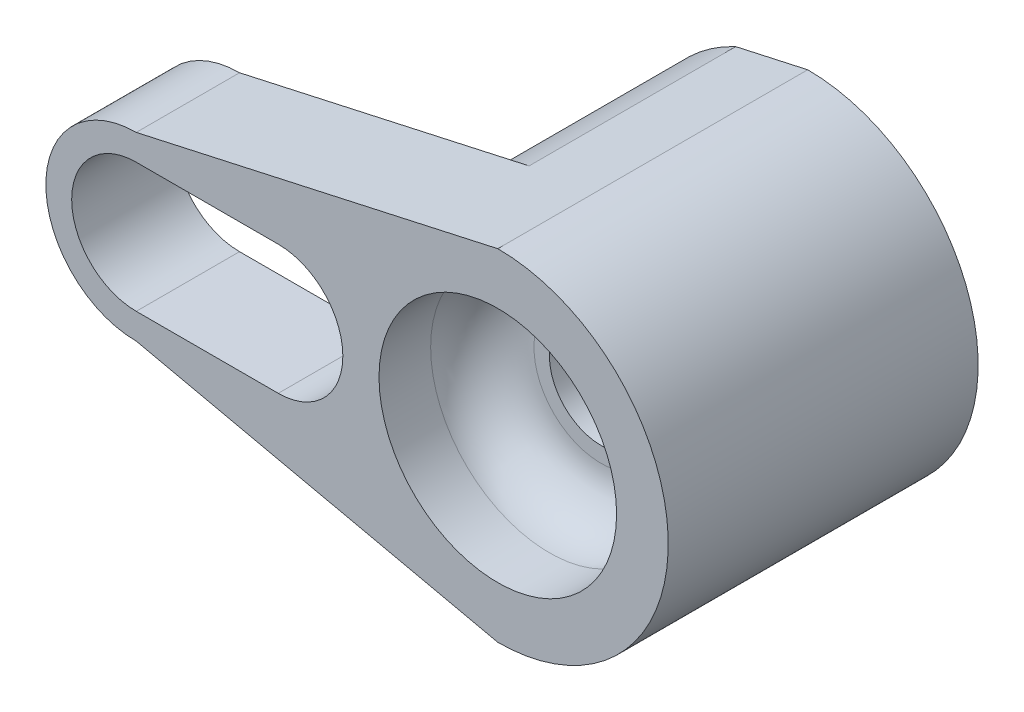
SolidWorks part; units mm, degrees
ref_plane "Ebene vorne" through (0, 0, 0) normal (0, 0, 1) x (1, 0, 0)
ref_plane "Ebene oben" through (0, 0, 0) normal (0, 1, 0) x (1, 0, 0)
ref_plane "Ebene rechts" through (0, 0, 0) normal (1, 0, 0) x (0, 0, -1)
sketch "Skizze1" plane through (0, 0, 0) normal (0, 0, 1) x (1, 0, 0)
  line L0 (0, 0) -> (-7, 0) construction
  line L1 (-7, 1.75) -> (0, 3.3)
  line L2 (-7, -1.75) -> (0, -3.3)
  line L3 (-7, 0) -> (-4.25, 0) construction
  line L4 (-7, 1.25) -> (-4.25, 1.25)
  line L5 (-7, -1.25) -> (-4.25, -1.25)
  circle A0 centre (0, 0) radius 3.3
  circle A1 centre (0, 0) radius 2.3
  arc A2 (-7, 1.75) -> (-7, -1.75) centre (-7, 0) ccw
  arc A3 (-7, 1.25) -> (-7, -1.25) centre (-7, 0) ccw
  circle A4 centre (0, 0) radius 1
  arc A5 (-4.25, -1.25) -> (-4.25, 1.25) centre (-4.25, 0) ccw
  point P10 (-5.625, 0)
  dimension "D1" = 4.6
  dimension "D2" = 1.25
  dimension "D4" = 1
  dimension "D6" = 2
  dimension "D7" = 0.5
  dimension "D5" = 7
  dimension "2,4" = 2.75
extrude "Aufsatz-Linear austragen1" add sketch "Skizze1" along normal blind 2 contours L1 A2 L2 A0 A5 L5 A3 L4 | L1 A0 L2 A1 region at (-4.1761, 2.2782, 0) region at (-0.6765, 3.0552, 0)
extrude "Aufsatz-Linear austragen2" add sketch "Skizze1<11>" against normal blind 4 contours L1 A0 L2 A1 region at (-0.6765, 3.0552, 0)
sketch "Skizze1<11>" plane through (0, 0, 0) normal (0, 0, 1) x (1, 0, 0) same geometry as "Skizze1"
extrude "Aufsatz-Linear austragen3" add sketch "Skizze1<13>" against normal blind 2 contours A1 A4 region at (-2.2349, 0, 0)
sketch "Skizze1<13>" plane through (0, 0, 0) normal (0, 0, 1) x (1, 0, 0) same geometry as "Skizze1"
fillet "Verrundung1" radius 1 1 edges at (2.3, 0, 0)
